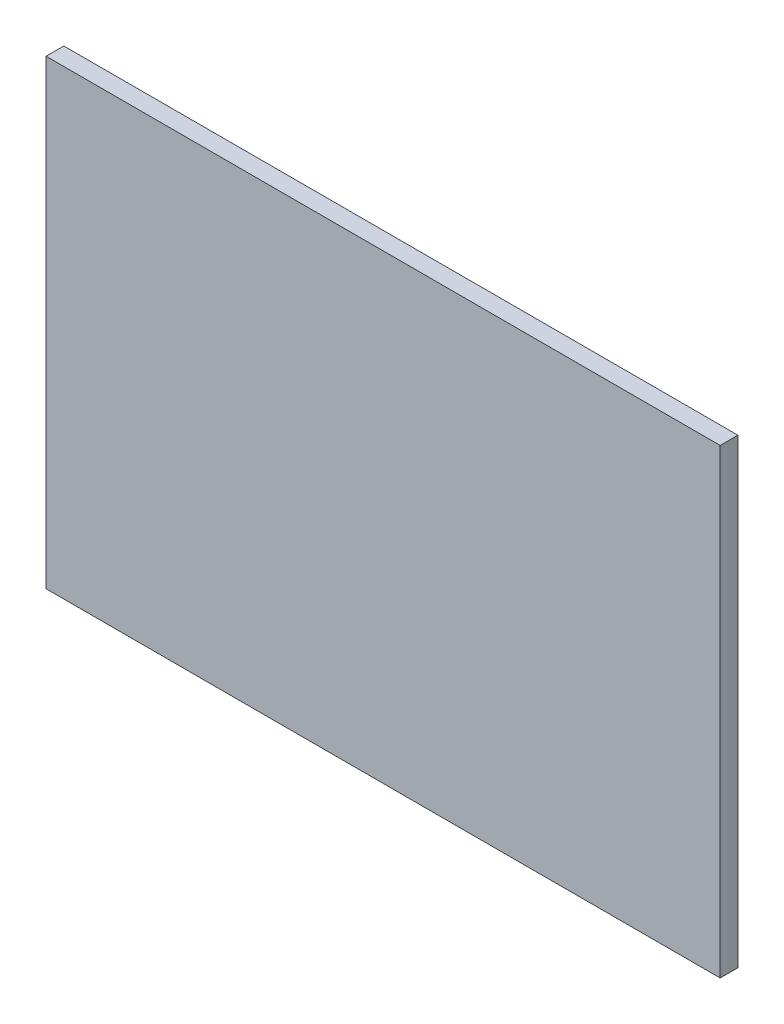
SolidWorks part; units mm, degrees
ref_plane "Front Plane" through (0, 0, 0) normal (0, 0, 1) x (1, 0, 0)
ref_plane "Top Plane" through (0, 0, 0) normal (0, 1, 0) x (1, 0, 0)
ref_plane "Right Plane" through (0, 0, 0) normal (1, 0, 0) x (0, 0, -1)
sketch "Sketch1" plane through (0, 0, 0) normal (0, 0, 1) x (1, 0, 0)
  line L1 (-19, -13) -> (19, -13)
  line L2 (-19, -13) -> (-19, 13)
  line L3 (-19, 13) -> (19, 13)
  line L4 (19, -13) -> (19, 13)
  line L5 (-19, -13) -> (19, 13) construction
  line L6 (-19, 13) -> (19, -13) construction
  point P0 (0, 0)
  dimension "D1" = 26
  dimension "D2" = 38
extrude "Boss-Extrude1" add sketch "Sketch1" along normal blind 1
sketch "Sketch3" plane through (0, 0, 0) normal (0, 1, 0) x (1, 0, 0)
  line L0 (0, 0) -> (70.7107, 70.7107)
  line L1 (0, 0) -> (-70.7107, 70.7107)
  line L2 (19, 0) -> (-19, 0) construction
  dimension "D1" = 45
  dimension "D2" = 100
  dimension "D3" = 100
ref_axis "Axis1" through (-564.8035, 0, 564.8035) along (0.7071, 0, -0.7071)
ref_axis "Axis2" through (0, 0, 0) along (-0.7071, 0, -0.7071)
ref_plane "Plane1" through (0, 0, 0) normal (-0.7071, 0, -0.7071) x (-0.7071, 0, 0.7071)
ref_plane "Plane2" through (0, 0, 0) normal (0, 1, 0) x (1, 0, 0)
ref_plane "Plane3" through (0, 0, 0) normal (0.7071, 0, -0.7071) x (-0.7071, 0, -0.7071)
